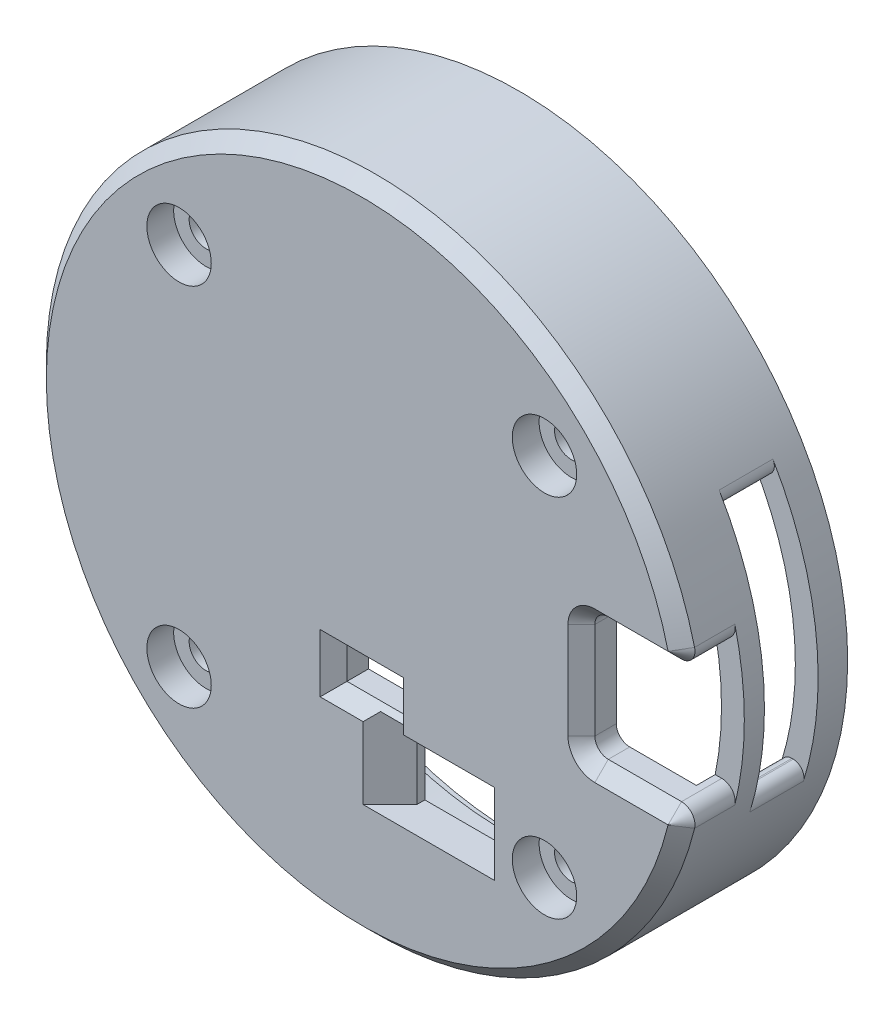
SolidWorks part; units mm, degrees
note: The reader was unsure of these and kept them because the rebuilt part matched: shared geometry of "草图2<5>", "草图2<6>", "草图2<7>", "草图2<20>", "草图2<9>", "草图2<13>", "草图2<18>", "草图2<14>", "草图2<19>".
material "可锻铸铁"
ref_plane "前视基准面" through (0, 0, 0) normal (0, 0, 1) x (1, 0, 0)
ref_plane "上视基准面" through (0, 0, 0) normal (0, 1, 0) x (1, 0, 0)
ref_plane "右视基准面" through (0, 0, 0) normal (1, 0, 0) x (0, 0, -1)
sketch "草图2" plane through (0, 0, 0) normal (0, 0, 1) x (1, 0, 0)
  line L0 (-36.168, 0) -> (40.0746, 0) construction
  line L1 (0, -37.0248) -> (0, 41.4439) construction
  line L2 (2.1, -9.65) -> (2.1, -15.65)
  line L3 (0, 0) -> (19.8165, 19.8165) construction
  line L4 (2.1, -15.65) -> (7.9, -15.65)
  line L5 (7.9, -15.65) -> (7.9, -9.65)
  line L6 (7.9, -9.65) -> (2.1, -9.65)
  line L7 (24.0643, 4.6) -> (16.3643, 4.6)
  line L8 (16.3643, 4.6) -> (16.3643, -4.6)
  line L9 (16.3643, -4.6) -> (24.0643, -4.6)
  line L10 (0, 0) -> (-9.0208, 10.3773) construction
  line L11 (19.8595, 11.2) -> (21.7901, 11.2)
  line L12 (21.9408, -6.2) -> (23.7025, -6.2)
  line L13 (-2.1, -6.9561) -> (-2.1, -9.3)
  line L14 (-2.1, -9.3) -> (2.1, -9.3)
  line L15 (2.1, -9.3) -> (2.1, -6.9561)
  line L16 (2.1, -6.9561) -> (-2.1, -6.9561)
  line L17 (0, 0) -> (9.0208, 10.3773) construction
  line L19 (0, 0) -> (-3.3264, -13.3416) construction
  circle A0 centre (0, 0) radius 24.5
  circle A2 centre (0, 0) radius 23.6
  circle A6 centre (0, 0) radius 19.25 construction
  circle A7 centre (0, 0) radius 22.8
  circle A8 centre (13.6118, 13.6118) radius 1.25
  circle A9 centre (13.6118, -13.6118) radius 1.25
  circle A10 centre (-13.6118, -13.6118) radius 1.25
  circle A11 centre (-13.6118, 13.6118) radius 1.25
  circle A12 centre (-13.6118, 13.6118) radius 2.7
  circle A13 centre (13.6118, 13.6118) radius 2.7
  circle A14 centre (13.6118, -13.6118) radius 2.7
  circle A15 centre (-13.6118, -13.6118) radius 2.7
  circle A16 centre (-13.6118, 13.6118) radius 2.4
  circle A17 centre (13.6118, 13.6118) radius 2.4
  circle A18 centre (13.6118, -13.6118) radius 2.4
  circle A19 centre (-13.6118, -13.6118) radius 2.4
  circle A20 centre (-9.0208, 10.3773) radius 2.3
  circle A21 centre (9.0208, 10.3773) radius 2.3
  circle A22 centre (-3.3264, -13.3416) radius 2.3
  circle A23 centre (0, 0) radius 13.75 construction
  point P24 (0, 0)
  point P32 (0, 0)
  point P39 (0, 0)
  point P57 (0, 0)
  point P80 (0, -19.25)
  dimension "D1" = 47.2
  dimension "D2" = 49
  dimension "D3" = 2.5
  dimension "D5" = 45.6
  dimension "D9" = 45
  dimension "D4" = 38.5
  dimension "D10" = 4
  dimension "D12" = 5.4
  dimension "D16" = 4.8
  dimension "D27" = 4.2
  dimension "D22" = 4.6
  dimension "D23" = 27.5
  dimension "D6" = 5.8
  dimension "D7" = 6
  dimension "D8" = 0.35
  dimension "D11" = 4.6
  dimension "D14" = 6.2
  dimension "D15" = 11.2
  dimension "D18" = 9.3
  dimension "D19" = 2.1
  dimension "D20" = 2.3439
  dimension "D21" = 7.7
  dimension "D24" = 41
  dimension "D25" = 41
  dimension "D26" = 14
  dimension "D13" = 4
  dimension "D17" = 4
extrude "凸台-拉伸3" add sketch "草图2" against normal blind 11.7 contours A2 L12 A0 L11 | A2 L11 A0 L12 | A2 L9 A0 L7 | A2 L12 A0 L9
extrude "凸台-拉伸4" add sketch "草图2<5>" against normal blind 10.7 contours A7 L11 A2 L12 | A7 L12 A2 L11 | A7 L9 A2 L7 | A7 L12 A2 L9
sketch "草图2<5>" plane through (0, 0, 0) normal (0, 0, 1) x (1, 0, 0) same geometry as "草图2"
extrude "凸台-拉伸5" add sketch "草图2<6>" against normal blind 2.6
sketch "草图2<6>" plane through (0, 0, 0) normal (0, 0, 1) x (1, 0, 0) same geometry as "草图2"
extrude "凸台-拉伸6" add sketch "草图2<7>" against normal blind 4 contours A17 A8 | A16 A11 | A18 A9 | A19 A10
sketch "草图2<7>" plane through (0, 0, 0) normal (0, 0, 1) x (1, 0, 0) same geometry as "草图2"
extrude "凸台-拉伸10" add sketch "草图2<20>" against normal blind 1.5 contours A20 | A21 | A22
sketch "草图2<20>" plane through (0, 0, 0) normal (0, 0, 1) x (1, 0, 0) same geometry as "草图2"
extrude "凸台-拉伸7" add sketch "草图2<9>" against normal blind 4 contours A12 A11 | A13 A8 | A12 A16 | A13 A17 | A14 A18 | A15 A19 | A19 A10 | A18 A9
sketch "草图2<9>" plane through (0, 0, 0) normal (0, 0, 1) x (1, 0, 0) same geometry as "草图2"
extrude "切除-拉伸2" cut sketch "草图2<13>" against normal blind 9.5 contours A2 L12 A0 L11 | A7 L12 A2 L11 | A7 L7 A2 L11 | A2 L7 A0 L11 | A7 L12 A2 L9 | A2 L12 A0 L9
sketch "草图2<13>" plane through (0, 0, 0) normal (0, 0, 1) x (1, 0, 0) same geometry as "草图2"
extrude "切除-拉伸3" cut sketch "草图2<18>" against normal blind 2 contours A17 A8 | A18 A9 | A19 A10 | A16 A11
sketch "草图2<18>" plane through (0, 0, 0) normal (0, 0, 1) x (1, 0, 0) same geometry as "草图2"
extrude "凸台-拉伸9" add sketch "草图2<14>" against normal blind 5.5 contours A2 L12 A0 L11 | A7 L12 A2 L11 | A2 L7 A0 L11 | A7 L7 A2 L11 | A2 L12 A0 L9 | A7 L12 A2 L9
sketch "草图2<14>" plane through (0, 0, 0) normal (0, 0, 1) x (1, 0, 0) same geometry as "草图2"
extrude "切除-拉伸4" cut sketch "草图2<19>" against normal blind 4 contours A7 L9 A2 L7 | A2 L9 A0 L7
sketch "草图2<19>" plane through (0, 0, 0) normal (0, 0, 1) x (1, 0, 0) same geometry as "草图2"
fillet "圆角2" radius 0.8 1 edges at (21.7901, 11.2, -7.5)
fillet "圆角3" radius 0.8 1 edges at (23.7025, -6.2, -7.5)
fillet "圆角4" radius 0.8 1 edges at (21.9408, -6.2, -7.5)
fillet "圆角5" radius 0.8 1 edges at (19.8595, 11.2, -7.5)
chamfer "倒角1" distance 2 angle 45 2 edges at (2.1, -12.65, 0) (7.9, -12.65, 0)
chamfer "倒角4" distance 1 angle 45 4 edges at (0, -9.3, 0) (2.1, -8.128, 0) (0, -6.9561, 0) (-2.1, -8.128, 0)
fillet "圆角6" radius 1 4 edges at (16.3643, 4.6, -1.3) (16.3643, -4.6, -1.3) (24.0643, 4.6, -2) (24.0643, -4.6, -2)
chamfer "倒角5" distance 1 angle 45 8 edges at (16.6572, 4.3071, 0) (16.3643, 0, 0) (16.6572, -4.3071, 0) (20.0937, -4.6, 0) (23.6099, -4.9829, 0) (20.0937, 4.6, 0) (23.6099, 4.9829, 0) (-24.5, 0, 0)
